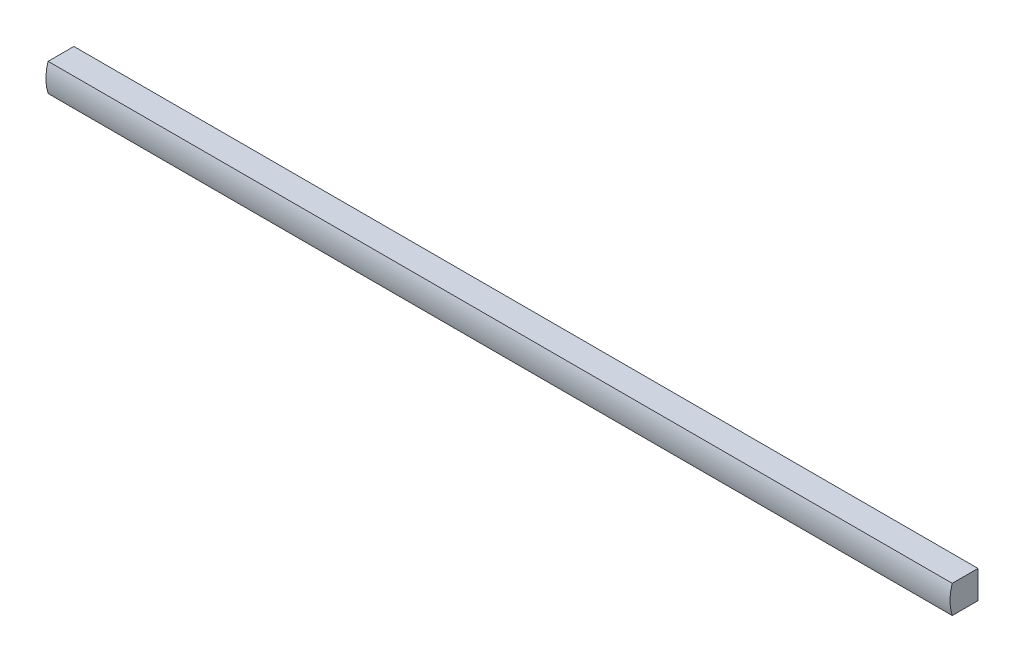
SolidWorks part; units mm, degrees
ref_plane "Front Plane" through (0, 0, 0) normal (0, 0, 1) x (1, 0, 0)
ref_plane "Top Plane" through (0, 0, 0) normal (0, 1, 0) x (1, 0, 0)
ref_plane "Right Plane" through (0, 0, 0) normal (1, 0, 0) x (0, 0, -1)
sketch "Sketch1" plane through (0, 0, 0) normal (1, 0, 0) x (0, 0, -1)
  line L1 (0, 0) -> (9.525, 0)
  line L2 (0, 0) -> (0, 9.525)
  line L3 (0, 9.525) -> (9.525, 9.525)
  line L4 (9.525, 0) -> (9.525, 9.525)
  arc A0 (0.7556, 0) -> (0.7426, 9.525) centre (15.5137, 4.7827) cw
  dimension "D2" = 8.7824
  dimension "D1" = 9.525
  dimension "D3" = 8.7694
extrude "Boss-Extrude1" add sketch "Sketch1" against normal blind 307.975 contours L1 L4 L3 L2 region at (0, 4.7636, -4.8835)
move or copy body "Body-Move/Copy1" [suppressed] bodies to move or copy 101 parameters "D1"=0, "D2"=0, "D3"=0
